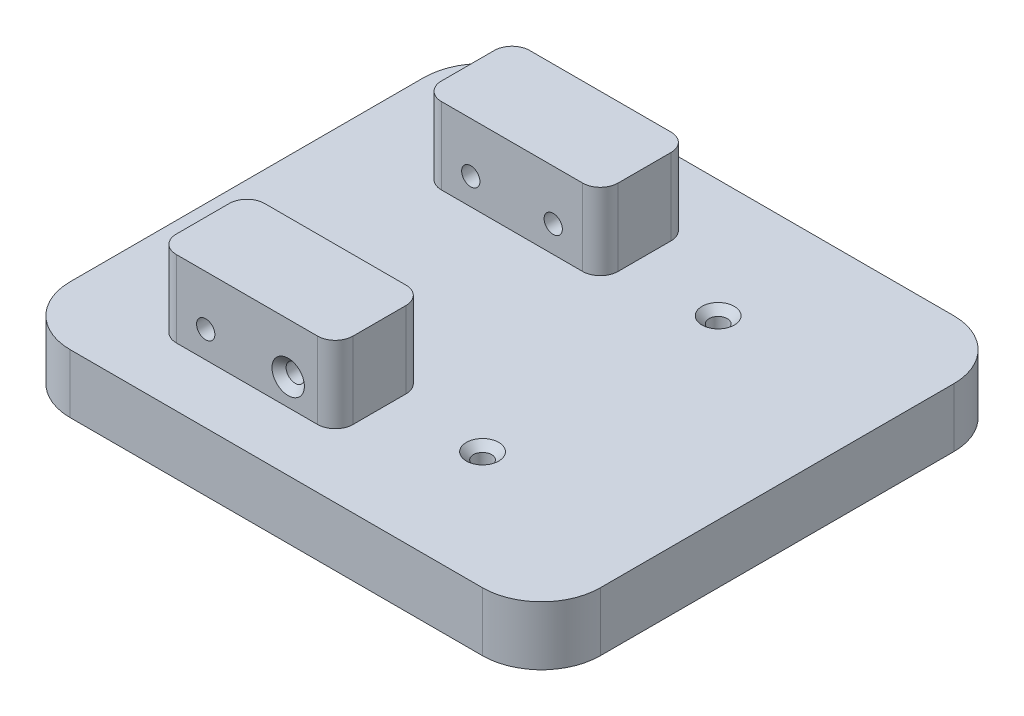
SolidWorks part; units mm, degrees
ref_plane "Piano frontale" through (0, 0, 0) normal (0, 0, 1) x (1, 0, 0)
ref_plane "Piano superiore" through (0, 0, 0) normal (0, 1, 0) x (1, 0, 0)
ref_plane "Piano destro" through (0, 0, 0) normal (1, 0, 0) x (0, 0, -1)
sketch "Schizzo1" plane through (0, 0, 0) normal (0, 1, 0) x (1, 0, 0)
  line L0 (-47.6, 35.6) -> (-47.6, -44.4)
  line L1 (-47.6, 35.6) -> (42.4, 35.6)
  line L2 (42.4, 35.6) -> (42.4, -44.4)
  line L3 (42.4, -44.4) -> (-47.6, -44.4)
  dimension "D1" = 80
  dimension "D2" = 90
extrude "Estrusione-Estrusione1" add sketch "Schizzo1" along normal blind 10
fillet "Raccordo1" radius 10 4 edges at (-47.6, 5, -35.6) (42.4, 5, -35.6) (-47.6, 5, 44.4) (42.4, 5, 44.4)
sketch "Schizzo2" plane through (0, 10, 0) normal (0, 1, 0) x (1, 0, 0)
  line L0 (12.4, -44.4) -> (12.4, 35.6) construction
  line L1 (-37.6, -44.4) -> (32.4, -44.4) construction
  line L2 (32.4, 35.6) -> (-37.6, 35.6) construction
  line L3 (-47.6, 25.6) -> (-47.6, -34.4) construction
  line L4 (12.4, -4.4) -> (-47.6, -4.4) construction
  line L5 (12.4, 15.6) -> (-47.6, 15.6) construction
  line L7 (12.4, -24.4) -> (-47.6, -24.4) construction
  dimension "D1" = 60
  dimension "D2" = 20
  dimension "D3" = 20
hole_wizard "Foro svasato per Vite M2.5-1" positions "Schizzo3D1" profile "Schizzo3" countersink size "M2.5" standard "IS" end condition through all
sketch3d "Schizzo3D1"
  point P0 (12.4, 10, -15.6)
  point P3 (12.4, 10, 24.4)
sketch "Schizzo3" plane through (12.4, 10, -15.6) normal (1, 0, 0) x (0, 0, 1)
  line L0 (0, 0) -> (0, 10)
  line L1 (0, 10) -> (1.55, 10)
  line L2 (1.55, 10) -> (1.55, 1.2)
  line L3 (1.55, 1.2) -> (2.75, 0)
  line L5 (2.75, 0) -> (0, 0)
  line L6 (-1.55, 1.2) -> (-2.75, 0) construction
  line L11 (0, -6.35) -> (0, 107.95) construction
  dimension "Thru Hole Dia." = 3.1
  dimension "Thru Hole Depth" = 10
  dimension "Near C'Sink Dia." = 5.5
  dimension "Near C'Sink Angle" = 90
sketch "Schizzo4" plane through (0, 10, 0) normal (0, 1, 0) x (1, 0, 0)
  line L0 (-32.6, 25.6) -> (-32.6, 10.6)
  line L1 (-32.6, 10.6) -> (-2.6, 10.6)
  line L2 (-2.6, 10.6) -> (-2.6, 25.6)
  line L3 (-2.6, 25.6) -> (-32.6, 25.6)
  line L4 (-2.6, -19.4) -> (-2.6, -34.4)
  line L5 (-2.6, -34.4) -> (-32.6, -34.4)
  line L6 (-32.6, -34.4) -> (-32.6, -19.4)
  line L7 (-32.6, -19.4) -> (-2.6, -19.4)
  line L8 (12.4, -24.4) -> (-47.6, -24.4) construction
  line L9 (12.4, 15.6) -> (-47.6, 15.6) construction
  line L10 (-47.6, 25.6) -> (-47.6, -34.4) construction
  dimension "D1" = 5
  dimension "D2" = 10
  dimension "D3" = 5
  dimension "D4" = 10
  dimension "D5" = 15
  dimension "D6" = 30
  dimension "D7" = 30
extrude "Estrusione-Estrusione2" add sketch "Schizzo4" along normal blind 13
sketch "Schizzo5" plane through (0, 0, -25.6) normal (0, 0, -1) x (-1, 0, 0)
  line L0 (32.6, 14.5) -> (2.6, 14.5) construction
  line L1 (2.6, 23) -> (2.6, 10) construction
  line L2 (10.6, 10) -> (10.6, 23) construction
  line L3 (-12.4, 10) -> (47.6, 10) construction
  line L4 (2.6, 23) -> (32.6, 23) construction
  line L6 (24.6, 10) -> (24.6, 23) construction
  line L7 (32.6, 23) -> (32.6, 10) construction
  point P10 (32.6, 12.5963)
  dimension "D1" = 4.5
  dimension "D2" = 8
  dimension "D3" = 8
sketch "Schizzo6" plane through (0, 0, 34.4) normal (0, 0, 1) x (1, 0, 0)
  line L0 (-32.6, 14.5) -> (-2.6, 14.5) construction
  line L2 (-10.6, 23) -> (-10.6, 10) construction
  line L4 (-24.6, 23) -> (-24.6, 10) construction
hole_wizard "Foro per Vite M2.5-1" positions "Schizzo3D2" profile "Schizzo8" hole size "M2.5" standard "IS"
sketch3d "Schizzo3D2"
  line L0 (-32.6, 14.5, -25.6) -> (-2.6, 14.5, -25.6) construction
  line L1 (-24.6, 10, -25.6) -> (-24.6, 23, -25.6) construction
  line L2 (-10.6, 10, -25.6) -> (-10.6, 23, -25.6) construction
  point P1 (-24.6, 14.5, -25.6)
  point P7 (-10.6, 14.5, -25.6)
sketch "Schizzo8" plane through (-24.6, 14.5, -25.6) normal (1, 0, 0) x (0, 1, 0)
  line L0 (0, 0) -> (0, 15.9313)
  line L1 (0, 15.9313) -> (1.55, 15)
  line L2 (1.55, 15) -> (1.55, 0)
  line L5 (1.55, 0) -> (0, 0)
  line L10 (0, 15.9313) -> (-1.55, 15) construction
  line L11 (0, -6.35) -> (0, 107.95) construction
  dimension "Hole Dia." = 3.1
  dimension "Hole Depth" = 15
  dimension "Drill Angle" = 118
hole_wizard "Foro per Vite M2.5-2" positions "Schizzo3D3" profile "Schizzo9" hole size "M2.5" standard "IS"
sketch3d "Schizzo3D3"
  line L0 (-32.6, 14.5, 34.4) -> (-2.6, 14.5, 34.4) construction
  line L1 (-24.6, 23, 34.4) -> (-24.6, 10, 34.4) construction
  point P0 (-24.6, 14.5, 34.4)
sketch "Schizzo9" plane through (-24.6, 14.5, 34.4) normal (1, 0, 0) x (0, -1, 0)
  line L0 (0, 0) -> (0, 15.9313)
  line L1 (0, 15.9313) -> (1.55, 15)
  line L2 (1.55, 15) -> (1.55, 0)
  line L5 (1.55, 0) -> (0, 0)
  line L10 (0, 15.9313) -> (-1.55, 15) construction
  line L11 (0, -6.35) -> (0, 107.95) construction
  dimension "Hole Dia." = 3.1
  dimension "Hole Depth" = 15
  dimension "Drill Angle" = 118
hole_wizard "Foro svasato per Vite M2.5-2" positions "Schizzo3D4" profile "Schizzo10" countersink size "M2.5" standard "IS"
sketch3d "Schizzo3D4"
  line L0 (-32.6, 14.5, 34.4) -> (-2.6, 14.5, 34.4) construction
  line L1 (-10.6, 23, 34.4) -> (-10.6, 10, 34.4) construction
  point P0 (-10.6, 14.5, 34.4)
sketch "Schizzo10" plane through (-10.6, 14.5, 34.4) normal (1, 0, 0) x (0, -1, 0)
  line L0 (0, 0) -> (0, 15.9313)
  line L1 (0, 15.9313) -> (1.55, 15)
  line L2 (1.55, 15) -> (1.55, 1.2)
  line L3 (1.55, 1.2) -> (2.75, 0)
  line L5 (2.75, 0) -> (0, 0)
  line L6 (-1.55, 1.2) -> (-2.75, 0) construction
  line L10 (0, 15.9313) -> (-1.55, 15) construction
  line L11 (0, -6.35) -> (0, 107.95) construction
  dimension "Hole Dia." = 3.1
  dimension "Hole Depth" = 15
  dimension "Near C'Sink Dia." = 5.5
  dimension "Near C'Sink Angle" = 90
  dimension "Drill Angle" = 118
fillet "Raccordo2" radius 3 8 edges at (-2.6, 16.5, -25.6) (-2.6, 16.5, -10.6) (-32.6, 16.5, -25.6) (-32.6, 16.5, -10.6) (-2.6, 16.5, 34.4) (-2.6, 16.5, 19.4) (-32.6, 16.5, 19.4) (-32.6, 16.5, 34.4)
